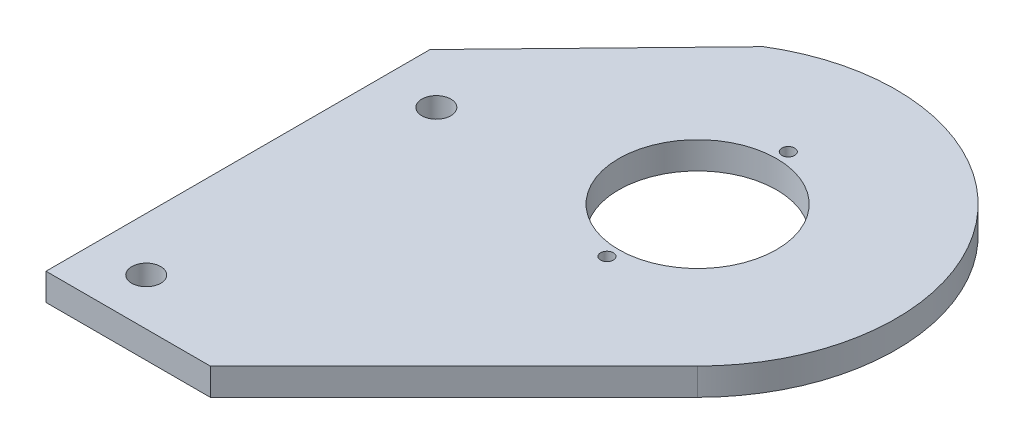
SolidWorks part; units mm, degrees
ref_plane "Front Plane" through (0, 0, 0) normal (0, 0, 1) x (1, 0, 0)
ref_plane "Top Plane" through (0, 0, 0) normal (0, 1, 0) x (1, 0, 0)
ref_plane "Right Plane" through (0, 0, 0) normal (1, 0, 0) x (0, 0, -1)
sketch "Sketch2" plane through (0, 0, 0) normal (0, 1, 0) x (1, 0, 0)
  line L0 (38.5109, 129.6827) -> (38.5109, 0) construction
  line L1 (0, 0) -> (38.5109, 0)
  line L2 (0, 0) -> (0, 90)
  line L3 (0, 129.6827) -> (38.5109, 129.6827) construction
  line L6 (95.6305, 57.1195) -> (38.5109, 0)
  line L8 (0, 129.6827) -> (0, 90) construction
  line L9 (0, 90) -> (62.75, 90) construction
  line L10 (0, 90) -> (38.5109, 129.6827)
  arc A1 (38.5109, 129.6827) -> (95.6305, 57.1195) centre (62.75, 90) cw
  dimension "D1" = 90
  dimension "D3" = 46.5
  dimension "D2" = 62.75
  dimension "D5" = 45
base flange "Base-Flange1" sketch "Sketch2" thickness 6.35 reverse thickness direction no parameters "D1"=0.7366
sketch "Sketch8" plane through (0, 0, 0) normal (0, 1, 0) x (1, 0, 0)
  line L1 (0, 90) -> (0, 0) construction
  line L2 (0, 45) -> (67.0707, 45) construction
  line L3 (0, 90) -> (109.25, 90) construction
  line L4 (67.0707, 28.5598) -> (67.0707, 90) construction
  line L5 (38.5109, 0) -> (95.6305, 57.1195) construction
  line L6 (0, 90) -> (0, 0) construction
  circle A1 centre (12.5, 79) radius 3.4
  circle A3 centre (12.5, 11) radius 3.4
  arc A4 (95.6305, 57.1195) -> (38.5109, 129.6827) centre (62.75, 90) ccw construction
  dimension "D1" = 6.8
  dimension "D3" = 12.5
  dimension "D2" = 11
extrude "Cut-Extrude1" cut sketch "Sketch8" against normal through all normal cut yes
sketch "Sketch9" plane through (0, 0, 0) normal (0, 1, 0) x (1, 0, 0)
  arc A0 (95.6305, 57.1195) -> (38.5109, 129.6827) centre (62.75, 90) ccw construction
  arc A1 (95.6305, 57.1195) -> (38.5109, 129.6827) centre (62.75, 90) ccw construction
  circle A2 centre (62.75, 90) radius 18.5
  dimension "D1" = 37
extrude "Cut-Extrude2" cut sketch "Sketch9" against normal through all normal cut yes
sketch "Sketch10" plane through (0, 0, 0) normal (0, 1, 0) x (1, 0, 0)
  circle A0 centre (62.75, 111.25) radius 1.5
  circle A1 centre (62.75, 68.75) radius 1.5
  circle A2 centre (62.75, 90) radius 18.5 construction
  circle A3 centre (62.75, 90) radius 18.5 construction
  circle A4 centre (62.75, 90) radius 21.25 construction
  dimension "D1" = 3
  dimension "D2" = 3
  dimension "D3" = 42.5
extrude "Cut-Extrude3" cut sketch "Sketch10" against normal through all normal cut yes
sketch "Bend-Lines1" [suppressed] plane through (0, 0, 0) normal (0, 1, 0) x (1, 0, 0)
sketch "Bounding-Box1" [suppressed] plane through (0, 0, 0) normal (0, 1, 0) x (1, 0, 0)
sheet metal parameters "Sheet-Metal1" thickness 6.35 parameters "D1"=0.7366
flat pattern "Flat-Pattern1" [suppressed]
sketch "Bend-Lines2" plane through (0, 0, 0) normal (0, 1, 0) x (1, 0, 0)
sketch3d "Bounding-Box2" [suppressed]
  line L0 (37.25, -37.25, 0) -> (37.25, 37.25, 0) construction
  line L1 (-22.5, -37.25, 0) -> (-22.5, 37.25, 0) construction
  line L2 (37.25, -37.25, 0) -> (-22.5, -37.25, 0) construction
  line L3 (37.25, 37.25, 0) -> (-22.5, 37.25, 0) construction
sheet metal parameters "Sheet-Metal2" thickness 6.35 parameters "D1"=0.7366
flat pattern "Flat-Pattern1"
sketch "Bend-Lines2" plane through (0, 0, 0) normal (0, 1, 0) x (1, 0, 0)
sketch3d "Bounding-Box2" [suppressed]
  line L0 (-107.7298, -46.3484, 0) -> (0.0689, 64.7304, 0) construction
  line L1 (-42.0452, -110.0934, 0) -> (65.7535, 0.9853, 0) construction
  line L2 (-107.7298, -46.3484, 0) -> (-42.0452, -110.0934, 0) construction
  line L3 (0.0689, 64.7304, 0) -> (65.7535, 0.9853, 0) construction
sheet metal parameters "Sheet-Metal3" thickness 6.35 parameters "D1"=0.7366
flat pattern "Flat-Pattern1"
sketch "Bend-Lines2" plane through (0, 0, 0) normal (0, 1, 0) x (1, 0, 0)
sketch3d "Bounding-Box2" [suppressed]
  line L0 (-107.7298, -46.3484, 0) -> (0.0689, 64.7304, 0) construction
  line L1 (-42.0452, -110.0934, 0) -> (65.7535, 0.9853, 0) construction
  line L2 (-107.7298, -46.3484, 0) -> (-42.0452, -110.0934, 0) construction
  line L3 (0.0689, 64.7304, 0) -> (65.7535, 0.9853, 0) construction
sheet metal parameters "Sheet-Metal4" thickness 6.35 parameters "D1"=0.7366
flat pattern "Flat-Pattern1"
sketch "Bend-Lines2" plane through (0, 0, 0) normal (0, 1, 0) x (1, 0, 0)
sketch3d "Bounding-Box2" [suppressed]
  line L0 (-107.7298, -46.3484, 0) -> (0.0689, 64.7304, 0) construction
  line L1 (-42.0452, -110.0934, 0) -> (65.7535, 0.9853, 0) construction
  line L2 (-107.7298, -46.3484, 0) -> (-42.0452, -110.0934, 0) construction
  line L3 (0.0689, 64.7304, 0) -> (65.7535, 0.9853, 0) construction
equation "\"L1L\"=500"
equation "\"L1Thick\"=6.35"
equation "\"Harm-Drive-Outer\"=74.5"
equation "\"L1-Spacing\"=115.65"
equation "\"L-Bracket-HoleToWall\"=12.5"
equation "\"Bracket-Hole-D\"=6.8"
equation "\"D1@Sketch8\"=\"Bracket-Hole-D\""
equation "\"L-Bracket-HoleToSide\"=11"
equation "\"D3@Sketch8\"=\"L-Bracket-HoleToWall\""
equation "\"D2@Sketch8\"=\"L-Bracket-HoleToSide\""
